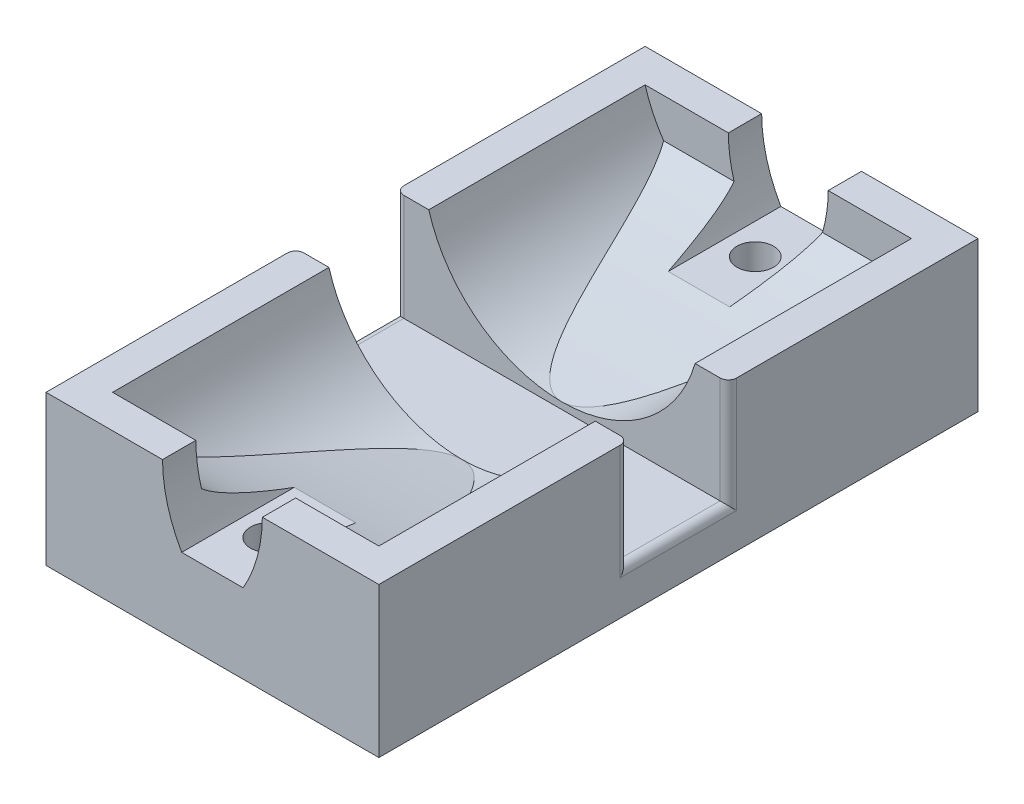
SolidWorks part; units mm, degrees
ref_plane "Front Plane" through (0, 0, 0) normal (0, 0, 1) x (1, 0, 0)
ref_plane "Top Plane" through (0, 0, 0) normal (0, 1, 0) x (1, 0, 0)
ref_plane "Right Plane" through (0, 0, 0) normal (1, 0, 0) x (0, 0, -1)
sketch "Sketch1" plane through (0, 0, 0) normal (0, 1, 0) x (1, 0, 0)
  line L0 (-185, -65) -> (5, -65)
  line L1 (-185, 135) -> (185, 135)
  line L2 (-185, 135) -> (-185, -65)
  line L4 (185, 135) -> (185, -135)
  line L8 (91.1823, -135) -> (185, -135)
  arc A0 (5, -65) -> (91.1823, -135) centre (5, -153.0528) cw
  point P0 (0, 0)
  point P1 (0, 0)
  point P3 (185, -98.2977)
  point P8 (91.1823, -135)
extrude "Boss-Extrude1" add sketch "Sketch1" along normal blind 15.0459
sketch "Sketch2" plane through (0, 15.0459, 0) normal (0, 1, 0) x (1, 0, 0)
  line L0 (-175, -35) -> (-175, 30)
  line L1 (-175, -35) -> (-142.5, -35)
  line L2 (-175, 125) -> (-142.5, 125)
  line L3 (-95, -35) -> (-95, 30)
  line L12 (-185, 135) -> (-185, -65) construction
  line L13 (-185, 135) -> (-142.5, 135)
  line L14 (-85, -45) -> (-85, 30)
  line L15 (-185, -45) -> (-142.5, -45)
  line L16 (-185, -45) -> (-185, 30)
  line L17 (-135, 196.4351) -> (-135, -108.7974) construction
  line L18 (-142.5, 135) -> (-142.5, 125)
  line L19 (-127.5, 135) -> (-127.5, 125)
  line L20 (-127.5, 135) -> (-85, 135)
  line L21 (-185, 135) -> (-85, 135) construction
  line L22 (-127.5, 125) -> (-95, 125)
  line L23 (-175, 125) -> (-95, 125) construction
  line L24 (-208.7616, 45) -> (-62.2564, 45) construction
  line L25 (-127.5, -45) -> (-127.5, -35)
  line L26 (-142.5, -45) -> (-142.5, -35)
  line L27 (-127.5, -35) -> (-95, -35)
  line L28 (-175, -35) -> (-95, -35) construction
  line L29 (-127.5, -45) -> (-85, -45)
  line L30 (-185, -45) -> (-85, -45) construction
  line L31 (185, 135) -> (-185, 135) construction
  line L32 (-175, 60) -> (-185, 60)
  line L33 (-175, 30) -> (-185, 30)
  line L34 (-95, 60) -> (-85, 60)
  line L35 (-95, 30) -> (-85, 30)
  line L36 (-175, 60) -> (-175, 125)
  line L37 (-175, -35) -> (-175, 125) construction
  line L38 (-185, 60) -> (-185, 135)
  line L39 (-185, -45) -> (-185, 135) construction
  line L40 (-85, 60) -> (-85, 135)
  line L41 (-85, -45) -> (-85, 135) construction
  line L42 (-95, 60) -> (-95, 125)
  line L43 (-95, -35) -> (-95, 125) construction
  point P14 (-135, 135.0621)
  point P18 (-175, 45)
  dimension "D1" = 160
  dimension "D2" = 80
  dimension "D3" = 10
  dimension "D4" = 7.5
  dimension "D5" = 50
  dimension "D6" = 30
  dimension "D7" = 15
extrude "Boss-Extrude2" add sketch "Sketch2" along normal blind 30
sketch "Sketch3" plane through (0, 0, -125) normal (0, 0, 1) x (1, 0, 0)
  line L0 (-127.5, 15.0459) -> (-142.5, 15.0459) construction
  line L4 (-142.5, 15.0459) -> (-142.5, 13.7784)
  line L7 (-142.5, 13.7784) -> (-127.5, 13.7784)
  line L8 (-175, 15.0459) -> (-142.5, 15.0459)
  line L9 (-142.5, 15.0459) -> (-142.5, 45.0459)
  line L10 (-142.5, 45.0459) -> (-175, 45.0459)
  line L11 (-175, 45.0459) -> (-175, 15.0459)
  line L12 (-175, 15.0459) -> (-142.5, 15.0459)
  line L14 (-142.5, 45.0459) -> (-175, 45.0459)
  line L15 (-175, 45.0459) -> (-175, 15.0459)
  line L16 (-127.5, 15.0459) -> (-95, 15.0459)
  line L17 (-95, 15.0459) -> (-95, 45.0459)
  line L18 (-95, 45.0459) -> (-127.5, 45.0459)
  line L19 (-127.5, 45.0459) -> (-127.5, 15.0459)
  line L20 (-127.5, 15.0459) -> (-95, 15.0459)
  line L21 (-95, 15.0459) -> (-95, 45.0459)
  line L22 (-95, 45.0459) -> (-127.5, 45.0459)
  line L24 (-127.5, 13.7784) -> (-127.5, 15.0459)
  line L27 (-142.5, 15.0459) -> (-142.5, 45.0459)
  line L28 (-127.5, 45.0459) -> (-127.5, 15.0459)
  arc A0 (-175, 45.0459) -> (-138.7313, 15.2133) centre (-135, 56.7125) ccw
  arc A1 (-131.2687, 15.2133) -> (-95, 45.0459) centre (-135, 56.7125) ccw
  arc A2 (-138.7313, 15.2133) -> (-131.2687, 15.2133) centre (-135, 56.7125) ccw
  point P0 (-135, 15.0459)
  line M9 (-175, 15.0459) -> (-142.5, 15.0459)
  line M10 (-142.5, 15.0459) -> (-142.5, 45.0459)
  line M12 (-175, 45.0459) -> (-175, 15.0459)
  dimension "D1" = 0
  dimension "D2" = 0
extrude "Boss-Extrude3" add sketch "Sketch3" along normal up to surface (160 mm away) contours A0 M12 M9 M10 | A0 L20 L21 | A0 M10 region at (-135, 14.539, -125) region at (-165.9764, 23.0143, -125) region at (-104.0236, 23.0143, -125) up to face at (-158.75, 30.0459, 35)
sketch "Sketch5" plane through (-185, 0, 0) normal (-1, 0, 0) x (0, 0, 1)
  line L0 (-60, 45.0459) -> (-30, 45.0459)
  line L10 (-135, 0) -> (65, 0)
  line L11 (65, 0) -> (65, 15.0459)
  line L12 (65, 15.0459) -> (45, 15.0459)
  line L13 (45, 15.0459) -> (45, 45.0459)
  line L14 (45, 45.0459) -> (-30, 45.0459)
  line L15 (-30, 45.0459) -> (-30, 15.0459)
  line L16 (-30, 15.0459) -> (-60, 15.0459)
  line L17 (-60, 15.0459) -> (-60, 45.0459)
  line L18 (-60, 45.0459) -> (-135, 45.0459)
  line L19 (-135, 45.0459) -> (-135, 0)
  line L25 (-30, 45.0459) -> (-30, 15.0459)
  line L26 (-30, 15.0459) -> (-60, 15.0459)
  line L27 (-60, 15.0459) -> (-60, 45.0459)
  dimension "D1" = 0
extrude "Cut-Extrude1" cut sketch "Sketch5" against normal through all both and the other way through all
sketch "Sketch6" plane through (0, 15.0459, 0) normal (0, 1, 0) x (1, 0, 0)
  line L0 (-85, 60) -> (-85, 30)
  line L1 (-200, -45) -> (-127.5, -45)
  line L18 (-85, 135) -> (-85, 60)
  line L19 (-85, 60) -> (-135, 60)
  line L21 (-185, 60) -> (-185, 30)
  line L22 (-185, 30) -> (-135, 30)
  line L24 (-85, 30) -> (-85, -45)
  line L25 (-85, 30) -> (-85, -45)
  line L26 (-85, -45) -> (-127.5, -45)
  line L27 (-85, -45) -> (-127.5, -45)
  line L28 (-135, 60) -> (-185, 60)
  line L29 (-135, 60) -> (-185, 60)
  line L30 (-135, 30) -> (-85, 30)
  line L31 (-185, -45) -> (-185, -65)
  line L32 (-185, -65) -> (5, -65)
  line L33 (91.1823, -135) -> (185, -135)
  line L34 (185, -135) -> (185, 135)
  line L35 (185, 135) -> (-85, 135)
  line L36 (-85, 135) -> (-85, 60)
  line L37 (-85, 60) -> (-135, 60)
  line L39 (-185, 60) -> (-185, 30)
  line L40 (-185, 30) -> (-135, 30)
  line L49 (-185, -45) -> (-185, -65)
  line L50 (-185, -65) -> (5, -65)
  line L51 (91.1823, -135) -> (185, -135)
  line L52 (185, -135) -> (185, 135)
  line L53 (185, 135) -> (-85, 135)
  line L54 (-135, 30) -> (-85, 30)
  line L55 (-127.5, -45) -> (-127.5, -35)
  line L56 (-127.5, -45) -> (-127.5, -35)
  line L57 (-127.5, -35) -> (-135, -35)
  line L58 (-127.5, -35) -> (-135, -35)
  line L59 (-135, -35) -> (-142.5, -35)
  line L60 (-135, -35) -> (-142.5, -35)
  line L61 (-142.5, -35) -> (-142.5, -45)
  line L62 (-142.5, -35) -> (-142.5, -45)
  line L63 (-142.5, -45) -> (-185, -45)
  line L64 (-142.5, -45) -> (-185, -45)
  arc A1 (91.1823, -135) -> (5, -65) centre (5, -153.0528) ccw
  arc A2 (91.1823, -135) -> (5, -65) centre (5, -153.0528) ccw
  line M20 (-85, 135) -> (-85, 60)
  line M26 (-85, 30) -> (-85, -45)
  line M27 (-85, -45) -> (-127.5, -45)
  line M32 (-142.5, -45) -> (-185, -45)
  line M33 (-185, -45) -> (-185, -65)
  line M34 (-185, -65) -> (5, -65)
  arc M35 (5, -65) -> (91.1823, -135) centre (5, -153.0528) cw
  line M36 (91.1823, -135) -> (185, -135)
  line M37 (185, -135) -> (185, 135)
  line M38 (185, 135) -> (-85, 135)
  dimension "D1" = 0
extrude "Cut-Extrude2" cut sketch "Sketch6" against normal blind 30 contours L1 L0 M32 M33 M34 M35 M36 M37 M38 M20 M26 M27 region at (53.7672, 15.0459, -15.5574)
sketch "Sketch8" plane through (0, 15.0459, 0) normal (0, 1, 0) x (1, 0, 0)
  line L6 (-135, 30) -> (-85, 30)
  line L7 (-85, 30) -> (-85, 60)
  line L8 (-85, 60) -> (-135, 60)
  line L9 (-135, 60) -> (-185, 60)
  line L10 (-185, 60) -> (-185, 30)
  line L11 (-135, 60) -> (-185, 60)
  line L12 (-135, 30) -> (-85, 30)
  line L13 (-85, 30) -> (-85, 60)
  line L14 (-85, 60) -> (-135, 60)
  line L16 (-185, 60) -> (-185, 30)
  line L18 (-185, 30) -> (-135, 30)
  line L19 (-185, 30) -> (-135, 30)
  dimension "D1" = 0
extrude "Cut-Extrude3" cut sketch "Sketch8" against normal blind 2.0105
sketch "Sketch9" plane through (0, 0, 45) normal (0, 0, 1) x (1, 0, 0)
  line L0 (-142.5, 45.0459) -> (-142.5, 15.0459) construction
  line L1 (-127.5, 45.0459) -> (-142.5, 45.0459)
  line L2 (-135, 51.2467) -> (-135, 10.8591) construction
  line L4 (-150, 45.0459) -> (-120, 45.0459)
  line L5 (-144.2328, 23.7882) -> (-125.7672, 23.7882)
  arc A0 (-150, 45.0459) -> (-144.2328, 23.7882) centre (-106.9594, 45.3116) ccw
  arc A1 (-120, 45.0459) -> (-125.7672, 23.7882) centre (-163.0406, 45.3116) cw
  point P4 (-142.5, 45.0459)
  point P5 (-135, 45.0459)
  point P15 (0, 0)
  dimension "D1" = 30
ref_plane "Plane1" through (0, 0, -45) normal (0, 0, 1) x (1, 0, 0)
ref_plane "Plane2" through (-135, 0, 0) normal (1, 0, 0) x (0, 0, -1)
sketch "Sketch11" plane through (0, 0, 45) normal (0, 0, 1) x (1, 0, 0)
  line L0 (-127.5, 45.0459) -> (-142.5, 45.0459) construction
  line L1 (-127.5, 45.0459) -> (-142.5, 45.0459)
  line L2 (-120, 45.0459) -> (-150, 45.0459)
  line L3 (-144.2328, 23.7882) -> (-125.7672, 23.7882)
  line L4 (-120, 45.0459) -> (-150, 45.0459)
  line L5 (-144.2328, 23.7882) -> (-125.7672, 23.7882)
  arc A2 (-125.7672, 23.7882) -> (-120, 45.0459) centre (-163.0406, 45.3116) ccw
  arc A3 (-150, 45.0459) -> (-144.2328, 23.7882) centre (-106.9594, 45.3116) ccw
  arc A4 (-125.7672, 23.7882) -> (-120, 45.0459) centre (-163.0406, 45.3116) ccw
  arc A5 (-150, 45.0459) -> (-144.2328, 23.7882) centre (-106.9594, 45.3116) ccw
  dimension "D1" = 0
sketch "Sketch12" plane through (-135, 0, 0) normal (1, 0, 0) x (0, 0, -1)
  line L0 (-35, 33.2724) -> (-35, 15.0079)
  line L1 (-35, 45.0459) -> (-35, 15.7264) construction
  line L2 (-35, 15.0079) -> (30, 15.0459)
  line L3 (30, 15.0459) -> (30, 45.0459) construction
  line L4 (30, 45.0459) -> (30, 13.0354) construction
  line L6 (-35, 33.2724) -> (-23.6227, 24.4577) construction
  line L7 (-23.6227, 24.4577) -> (30, 15.0459) construction
  spline S0 degree 2 poles (-35, 33.2724) (-23.6227, 24.4577) (30, 15.0459) knots 0 0 0 1 1 1
  point P9 (-18.1361, 17.6735)
  point P10 (-23.6227, 24.4577)
extrude "Boss-Extrude6" add sketch "Sketch12" along normal up to next and the other way up to surface other way up to face at (-185, 25.7818, -45)
sketch "Sketch13" plane through (0, 0, 45) normal (0, 0, 1) x (1, 0, 0)
  line L0 (-142.5, 45.0459) -> (-127.5, 45.0459)
  line L8 (-185, 45.0459) -> (-185, 0)
  line L9 (-185, 0) -> (-85, 0)
  line L10 (-85, 0) -> (-85, 45.0459)
  line L11 (-85, 45.0459) -> (-127.5, 45.0459)
  line L12 (-127.5, 45.0459) -> (-127.5, 15.0459)
  line L13 (-127.5, 15.0459) -> (-142.5, 15.0459)
  line L14 (-142.5, 15.0459) -> (-142.5, 45.0459)
  line L15 (-142.5, 45.0459) -> (-185, 45.0459)
  line L20 (-127.5, 45.0459) -> (-127.5, 15.0459)
  line L21 (-127.5, 15.0459) -> (-142.5, 15.0459)
  line L22 (-142.5, 15.0459) -> (-142.5, 45.0459)
  dimension "D1" = 0
extrude "Boss-Extrude7" add sketch "Sketch13" against normal up to surface (10 mm away) up to face at (-157.4777, 39.1046, 35)
sketch "Sketch14" plane through (0, 0, -135) normal (0, 0, -1) x (-1, 0, 0)
  line L0 (142.5, 45.0459) -> (127.5, 45.0459)
  line L8 (85, 45.0459) -> (85, 0)
  line L9 (85, 0) -> (185, 0)
  line L10 (185, 0) -> (185, 45.0459)
  line L11 (185, 45.0459) -> (142.5, 45.0459)
  line L12 (142.5, 45.0459) -> (142.5, 15.0459)
  line L13 (142.5, 15.0459) -> (127.5, 15.0459)
  line L14 (127.5, 15.0459) -> (127.5, 45.0459)
  line L15 (127.5, 45.0459) -> (85, 45.0459)
  line L20 (142.5, 45.0459) -> (142.5, 15.0459)
  line L21 (142.5, 15.0459) -> (127.5, 15.0459)
  line L22 (127.5, 15.0459) -> (127.5, 45.0459)
  dimension "D1" = 0
extrude "Boss-Extrude8" add sketch "Sketch14" against normal up to surface (10 mm away) up to face at (-154.72, 33.7356, -125)
mirror "Mirror3" about plane through (0, 0, -45) normal (0, 0, 1) of "Boss-Extrude6"
extrude "Cut-Extrude6" cut sketch "Sketch9" against normal blind 192 contours A0 L5 A1 L4
sketch "Sketch18" plane through (0, 0, 0) normal (0, -1, 0) x (1, 0, 0)
  line L1 (-135, 11.1736) -> (-135, 57.7469) construction
  line L2 (-125.7672, 11.1736) -> (-144.2328, 11.1736) construction
  circle A0 centre (-135, 28.0736) radius 3
  point P2 (-135, 27.5588)
  dimension "D1" = 6
  dimension "D2" = 16.9
extrude "Cut-Extrude7" cut sketch "Sketch18" against normal blind 192
ref_plane "Plane3" through (0, 16, 0) normal (0, -1, 0) x (-1, 0, 0)
sketch "Sketch19" plane through (0, 16, 0) normal (0, -1, 0) x (-1, 0, 0)
  circle A0 centre (135, -28.0736) radius 5.5
  dimension "D1" = 11
extrude "Cut-Extrude8" cut sketch "Sketch19" against normal up to next
mirror "Mirror4" about plane through (0, 0, -45) normal (0, 0, 1) of "Cut-Extrude7", "Cut-Extrude8"
fillet "Fillet2" radius 2.5 6 edges at (-185, 29.0406, -30) (-85, 29.0406, -30) (-85, 29.0406, -60) (-185, 29.0406, -60) (-85, 13.0354, -45) (-185, 13.0354, -45)
